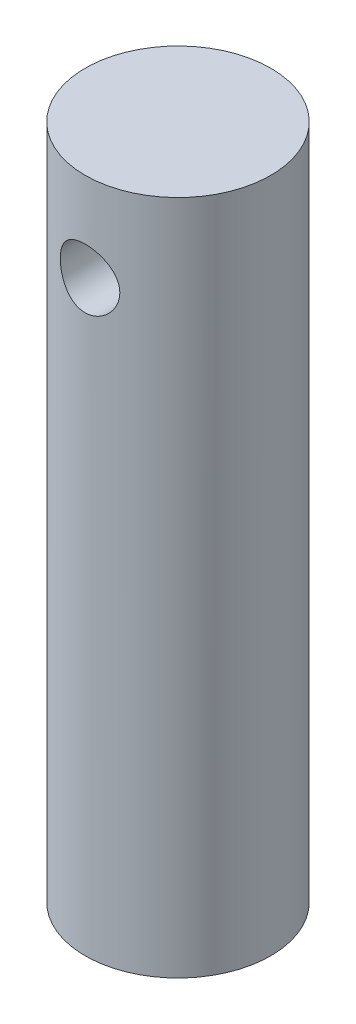
SolidWorks part; units mm, degrees
note: '?' marks a value the reader was unsure of. The reader was unsure of these and kept them because the rebuilt part matched: shared geometry of "Sketch1<3>", "Sketch41<11>", "Sketch41<12>", "Sketch45<3>".
ref_plane "Front Plane" through (0, 0, 0) normal (0, 0, 1) x (1, 0, 0)
ref_plane "Top Plane" through (0, 0, 0) normal (0, 1, 0) x (1, 0, 0)
ref_plane "Right Plane" through (0, 0, 0) normal (1, 0, 0) x (0, 0, -1)
sketch "Sketch1" plane through (0, 0, 0) normal (0, 1, 0) x (1, 0, 0)
  line L0 (0, 32.639) -> (7.239, 39.878)
  line L1 (7.239, 0) -> (55.118, 0)
  line L2 (0, 7.239) -> (0, 32.639)
  line L3 (7.239, 39.878) -> (55.118, 39.878)
  line L4 (7.239, 0) -> (0, 7.239)
  arc A0 (55.118, 0) -> (55.118, 39.878) centre (55.118, 19.939) ccw
  point P0 (0, 0)
  point P2 (0, 39.878)
  dimension "D1" = 55.118
  dimension "D2" = 39.878
extrude "Boss-Extrude1" add sketch "Sketch1" along normal blind 6.35
sketch "Sketch6" plane through (0, 6.35, 0) normal (0, 1, 0) x (1, 0, 0)
  circle A0 centre (55.118, 19.939) radius 19.431
extrude "Boss-Extrude4" add sketch "Sketch6" along normal blind 0.762 separate body contours A0
sketch "Sketch7" plane through (0, 7.112, 0) normal (0, 1, 0) x (1, 0, 0)
  circle A0 centre (55.118, 19.939) radius 19.05
  dimension "D1" = 38.1
extrude "Boss-Extrude5" add sketch "Sketch7" along normal blind 68.326 separate body
sketch "Sketch8" plane through (0, 75.438, 0) normal (0, 1, 0) x (1, 0, 0)
  circle A0 centre (55.118, 19.939) radius 4.953
  dimension "D1" = 9.906
fillet "Fillet6" radius 5.08 2 edges at (0, 3.175, -7.239) (0, 3.175, -32.639)
fillet "Fillet7" radius 1.905 2 edges at (7.239, 3.175, -39.878) (7.239, 3.175, 0)
sketch "Sketch15" plane through (0, 6.35, 0) normal (0, 1, 0) x (1, 0, 0)
  line L0 (35.5603, 29.0153) -> (35.5603, 29.0265)
  line L2 (0, 30.5348) -> (0, 9.3432) construction
  line L3 (0, 19.939) -> (0, 10.2869)
  line L4 (0, 19.939) -> (0, 29.591)
  line L5 (0, 10.2869) -> (16.412, 5.5423)
  line L7 (35.5603, 10.8628) -> (35.5603, 10.8515)
  line L10 (0, 29.591) -> (16.4119, 34.3357)
  arc A0 (16.412, 5.5423) -> (16.4119, 34.3357) centre (20.574, 19.939) ccw
ref_plane "Plane4" through (13.8375, 0, -51.6424) normal (0.2588, 0, -0.9659) x (0, -1, 0)
ref_plane "Plane5" through (12.5227, 0, -46.7355) normal (0.2588, 0, -0.9659) x (0, -1, 0)
sketch "Sketch23" plane through (12.5227, 0, -46.7355) normal (0.2588, 0, -0.9659) x (0, -1, 0)
  line L0 (-6.35, -67.5103) -> (-6.35, -28.6483) construction
  line L1 (-2.032, -53.8839) -> (5.588, -53.8839)
  line L2 (-2.032, -53.8839) -> (-2.032, -42.4539)
  line L3 (-2.032, -42.4539) -> (5.588, -42.4539)
  arc A0 (5.588, -53.8839) -> (5.588, -42.4539) centre (5.588, -48.1689) ccw
  dimension "D1" = 11.43
  dimension "D2" = 7.62
  dimension "D3" = 4.318
extrude "Boss-Extrude15" add sketch "Sketch23" along normal blind 6.35
sketch "Sketch24" plane through (14.1662, 0, -52.8692) normal (0.2588, 0, -0.9659) x (-0.9659, 0, -0.2588)
  circle A0 centre (-48.1689, -5.588) radius 4.064
  dimension "D1" = 8.128
extrude "Boss-Extrude16" add sketch "Sketch24" along normal blind 10.16
sketch "Sketch25" plane through (16.7959, 0, -62.683) normal (0.2588, 0, -0.9659) x (-0.9659, 0, -0.2588)
  circle A0 centre (-48.1689, -5.588) radius 2.54
  dimension "D1" = 5.08
extrude "Boss-Extrude17" add sketch "Sketch25" along normal blind 10.16
extrude "Boss-Extrude19" add sketch "Sketch1<3>" against normal blind 16.51 separate body
sketch "Sketch1<3>" plane through (0, 0, 0) normal (0, 1, 0) x (1, 0, 0) same geometry as "Sketch1"
fillet "Fillet13" radius 1.905 2 edges at (7.239, -8.255, 0) (7.239, -8.255, -39.878)
fillet "Fillet14" radius 5.08 2 edges at (0, -8.255, -32.639) (0, -8.255, -7.239)
sketch "Sketch26" plane through (0, -16.51, 0) normal (0, -1, 0) x (-1, 0, 0)
  line L4 (-20.574, 28.829) -> (-11.684, 28.829)
  line L5 (-20.574, 28.829) -> (-29.464, 28.829)
  line L6 (-11.684, 28.829) -> (-11.684, 11.049)
  line L7 (-11.684, 11.049) -> (-29.464, 11.049)
  line L8 (-29.464, 11.049) -> (-29.464, 28.829)
extrude "Boss-Extrude20" add sketch "Sketch26" along normal blind 18.796 separate body
chamfer "Chamfer1" distance 2.54 angle 45 4 edges at (29.464, -25.908, -28.829) (29.464, -25.908, -11.049) (11.684, -25.908, -11.049) (11.684, -25.908, -28.829)
fillet "Fillet15" radius 2.54 8 edges at (11.684, -25.908, -13.589) (14.224, -25.908, -11.049) (26.924, -25.908, -11.049) (29.464, -25.908, -13.589) (29.464, -25.908, -26.289) (26.924, -25.908, -28.829) (11.684, -25.908, -26.289) (14.224, -25.908, -28.829)
chamfer "Chamfer2" distance 0.762 angle 45 16 edges at (14.3041, -35.306, -11.2423) (20.574, -35.306, -11.049) (26.8439, -35.306, -11.2423) (28.194, -35.306, -12.319) (29.2707, -35.306, -13.6691) (29.464, -35.306, -19.939) (29.2707, -35.306, -26.2089) (28.194, -35.306, -27.559) (26.8439, -35.306, -28.6357) (20.574, -35.306, -28.829) (14.3041, -35.306, -28.6357) (12.954, -35.306, -27.559) (11.8773, -35.306, -26.2089) (11.684, -35.306, -19.939) (11.8773, -35.306, -13.6691) (12.954, -35.306, -12.319)
sketch "Sketch27" plane through (0, 0, -11.049) normal (0, 0, 1) x (1, 0, 0)
  circle A0 centre (20.574, -26.67) radius 3.175
extrude "Cut-Extrude3" cut sketch "Sketch27" against normal blind 19.05
sketch "Sketch28" plane through (0, 75.438, 0) normal (0, 1, 0) x (1, 0, 0)
  circle A0 centre (55.118, 19.939) radius 19.05
extrude "Boss-Extrude22" add sketch "Sketch28" along normal blind 1.27 separate body
sketch "Sketch29" plane through (0, 76.708, 0) normal (0, 1, 0) x (1, 0, 0)
  circle A0 centre (55.118, 19.939) radius 19.05
extrude "Boss-Extrude24" add sketch "Sketch29" along normal blind 3.048 separate body contours A0
extrude "Boss-Extrude25" add sketch "Sketch8" along normal blind 1.27 from surface at 4.318 contours A0 starting at face at (55.118, 79.756, -0.889)
fillet "Fillet16" radius 0.2286 1 edges at (55.118, 81.026, -14.986)
extrude "Boss-Extrude26" add sketch "Sketch15" along normal blind 254.381 separate body contours L5 A0 L10 L4 L3
sketch "Sketch32" plane through (0, 260.731, 0) normal (0, 1, 0) x (1, 0, 0)
  line L0 (0, 10.2869) -> (0, 29.591)
  line L1 (0, 29.591) -> (16.4119, 34.3357)
  line L2 (0, 10.2869) -> (16.412, 5.5423)
  arc A0 (16.412, 5.5423) -> (16.4119, 34.3357) centre (20.574, 19.939) ccw
extrude "Boss-Extrude27" add sketch "Sketch32" along normal blind 8.89 separate body
sketch "Sketch33" plane through (0, 269.621, 0) normal (0, 1, 0) x (1, 0, 0)
  circle A0 centre (20.574, 19.939) radius 9.906
extrude "Boss-Extrude28" add sketch "Sketch33" along normal blind 21.336
sketch3d "3DSketch1" plane through (0, 0, 0) normal (0, 0, 1) x (1, 0, 0)
sketch "Sketch41" plane through (0, 6.35, 0) normal (0, 1, 0) x (1, 0, 0)
  line L0 (16.4119, 34.3357) -> (0, 29.591)
  line L1 (37.5429, 9.0662) -> (33.7712, 12.8379)
  line L2 (0.2737, 32.0497) -> (15.777, 36.5318)
  line L3 (37.5429, 9.0662) -> (31.2567, 2.78)
  line L4 (0, 29.591) -> (0, 30.5348)
  line L5 (0, 30.5348) -> (0.2737, 32.0497)
  line L6 (-0.6349, 31.7871) -> (15.777, 36.5318) construction
  line L7 (0, 19.9389) -> (7.9017, 19.9389)
  line L8 (31.2567, 2.78) -> (27.426, 6.6107)
  line L9 (0, 10.2869) -> (0, 29.591) construction
  line L10 (0, 10.2869) -> (0, 9.3431)
  line L12 (37.5429, 30.8116) -> (33.7712, 27.0399)
  line L13 (37.5429, 30.8116) -> (31.2567, 37.0978)
  line L14 (31.2567, 37.0978) -> (27.426, 33.2671)
  line L15 (0, 9.3431) -> (0.2737, 7.8281)
  line L16 (0.2737, 7.8281) -> (15.777, 3.3461)
  line L17 (16.4119, 5.5422) -> (0, 10.2869)
  line L18 (-0.6349, 8.0908) -> (15.7771, 3.3462) construction
  line L19 (27.426, 33.2671) -> (29.1122, 34.9533)
  line L20 (0, 29.591) -> (16.4119, 34.3357) construction
  line L21 (0, 10.2869) -> (16.412, 5.5423) construction
  arc A0 (16.4119, 34.3357) -> (33.7712, 27.0399) centre (20.574, 19.939) cw
  arc A1 (15.777, 36.5318) -> (29.1122, 34.9533) centre (20.574, 19.939) cw
  arc A2 (16.4119, 34.3357) -> (16.412, 5.5423) centre (20.574, 19.939) cw construction
  arc A3 (15.777, 36.5318) -> (15.7771, 3.3462) centre (20.574, 19.939) cw construction
  arc A4 (16.4119, 34.3357) -> (27.426, 33.2671) centre (20.574, 19.939) cw
  arc A5 (15.777, 3.3461) -> (29.1122, 4.9245) centre (20.574, 19.9389) ccw
  arc A6 (16.4119, 5.5422) -> (33.7712, 12.8379) centre (20.574, 19.9389) ccw
  line M5 (0, 30.5348) -> (0, 9.3432)
  arc M6 (0, 9.3432) -> (1.4879, 5.7511) centre (5.08, 9.3432) ccw
extrude "Boss-Extrude30" add sketch "Sketch41" along normal blind 2.159 separate body contours A1 L2 L5 L0 A0 L14 M5
extrude "Boss-Extrude31" add sketch "Sketch41<11>" along normal blind 2.159 separate body contours A6 L17 L15 L16 A5 L8 M5 M6
sketch "Sketch41<11>" plane through (0, 6.35, 0) normal (0, 1, 0) x (1, 0, 0) same geometry as "Sketch41"
extrude "Boss-Extrude33" add sketch "Sketch41<12>" along normal blind 12.7 separate body contours L14 A0 L12 L13 | A6 L8 L3 L1
sketch "Sketch41<12>" plane through (0, 6.35, 0) normal (0, 1, 0) x (1, 0, 0) same geometry as "Sketch41"
fillet "Fillet17" radius 0.2286 5 edges at (35.657, 19.05, -28.9258) (29.3413, 19.05, -35.1825) (34.3998, 19.05, -33.9547) (37.5429, 12.7, -30.8116) (31.2567, 12.7, -37.0978)
fillet "Fillet18" radius 0.2286 5 edges at (35.657, 19.05, -10.9521) (29.3413, 19.05, -4.6954) (37.5429, 12.7, -9.0662) (34.3998, 19.05, -5.9231) (31.2567, 12.7, -2.78)
sketch "Sketch43" plane through (34.1773, 0, -34.1773) normal (0.7071, 0, -0.7071) x (-0.7071, 0, -0.7071)
  circle A0 centre (-0.3147, 13.7414) radius 3.175
extrude "Boss-Extrude34" add sketch "Sketch43" along normal blind 1.27 separate body
fillet "Fillet19" radius 1.27 1 edges at (33.0527, 13.7414, -37.0978)
sketch "Sketch44" plane through (14.2383, 0, 14.2383) normal (0.7071, 0, 0.7071) x (0.7071, 0, -0.7071)
  circle A0 centre (28.5126, 13.7414) radius 3.175
extrude "Boss-Extrude35" add sketch "Sketch44" along normal blind 1.27 separate body
fillet "Fillet20" radius 1.27 1 edges at (37.5429, 13.7414, -7.2702)
sketch "Sketch45" plane through (0, -16.51, 0) normal (0, -1, 0) x (1, 0, 0)
  line L0 (4.0845, -36.7235) -> (6.681, -39.32)
  line L2 (6.681, -39.32) -> (1.4879, -34.1269) construction
  line L4 (55.118, -39.878) -> (8.0281, -39.878) construction
  line L5 (11.3938, -39.878) -> (8.0281, -39.878)
  line L6 (11.3938, 0) -> (8.0281, 0)
  line L7 (4.0845, -3.1545) -> (6.681, -0.558)
  arc A0 (11.2821, -38.9146) -> (11.3938, -39.878) centre (11.8197, -39.3405) ccw
  arc A1 (11.2821, -38.9146) -> (5.0443, -35.9783) centre (8.8543, -35.9783) ccw
  arc A2 (11.2821, -0.9634) -> (11.3938, 0) centre (11.8197, -0.5375) cw
  arc A3 (5.0443, -35.9783) -> (4.0845, -36.7235) centre (4.1918, -35.871) cw
  arc A4 (5.0443, -3.8997) -> (4.0845, -3.1545) centre (4.1918, -4.007) ccw
  arc A5 (11.2821, -0.9634) -> (5.0443, -3.8997) centre (8.8543, -3.8997) cw
  arc A6 (55.118, -39.878) -> (55.118, 0) centre (55.118, -19.939) ccw construction
  arc A7 (73.6621, -16.9922) -> (73.6621, -22.8858) centre (71.247, -19.939) ccw
  arc A8 (73.6621, -22.8858) -> (74.7121, -23.6317) centre (73.8141, -23.7837) cw
  arc A9 (73.6621, -16.9922) -> (74.7121, -16.2463) centre (73.8141, -16.0943) ccw
  arc A10 (8.0281, -39.878) -> (6.681, -39.32) centre (8.0281, -37.973) cw
  arc A11 (8.0281, 0) -> (6.681, -0.558) centre (8.0281, -1.905) ccw
  arc A12 (74.7121, -23.6317) -> (74.7121, -16.2463) centre (55.118, -19.939) ccw
  line M8 (1.4879, -34.1269) -> (6.681, -39.32)
  arc M9 (6.681, -39.32) -> (8.0281, -39.878) centre (8.0281, -37.973) ccw
  line M10 (8.0281, -39.878) -> (55.118, -39.878)
  line M12 (55.118, 0) -> (8.0281, 0)
  arc M13 (8.0281, 0) -> (6.681, -0.558) centre (8.0281, -1.905) ccw
  line M14 (6.681, -0.558) -> (1.4879, -5.7511)
extrude "Cut-Extrude5" cut sketch "Sketch45" against normal blind 2.54 contours A1 A3 A0 M8 M9 M10 | A5 A2 A4 M12 M13 M14
extrude "Cut-Extrude6" cut sketch "Sketch45<3>" against normal blind 2.54
sketch "Sketch45<3>" plane through (0, -16.51, 0) normal (0, -1, 0) x (1, 0, 0) same geometry as "Sketch45"
sketch "Sketch47" plane through (0, -13.97, 0) normal (0, -1, 0) x (-1, 0, 0)
  circle A0 centre (-8.8543, 35.9783) radius 2.54
  circle A1 centre (-8.8543, 3.8997) radius 2.54
  circle A2 centre (-71.247, 19.939) radius 2.54
extrude "Boss-Extrude36" add sketch "Sketch47" along normal blind 2.54 separate body
fillet "Fillet22" radius 1.524 1 edges at (8.8543, -16.51, -38.5183)
fillet "Fillet23" radius 1.524 1 edges at (8.8543, -16.51, -6.4397)
sketch "Sketch48" plane through (0, 0, 0) normal (-1, 0, 0) x (0, 0, 1)
  circle A0 centre (-19.939, 12.7) radius 3.81
extrude "Boss-Extrude37" add sketch "Sketch48" along normal blind 1.524
fillet "Fillet24" radius 1.524 1 edges at (-1.524, 12.7, -16.129)
fillet "Fillet25" radius 1.524 1 edges at (71.247, -16.51, -22.479)
sketch "Sketch49" plane through (0, 0, 0) normal (-1, 0, 0) x (0, 0, 1)
  line L0 (-19.9389, 260.731) -> (-19.9389, 255.778) construction
  line L1 (-29.591, 260.731) -> (-10.2869, 260.731) construction
  line L2 (-30.5348, 6.35) -> (-9.3432, 6.35) construction
  circle A0 centre (-19.9389, 255.778) radius 3.81
  dimension "Flat Head Screw" = 249.428
extrude "Cut-Extrude7" cut sketch "Sketch49" against normal blind 2.54
sketch "Sketch50" plane through (2.54, 0, 0) normal (-1, 0, 0) x (0, 0, 1)
  circle A0 centre (-19.9389, 255.778) radius 3.556
extrude "Boss-Extrude39" add sketch "Sketch50" along normal blind 2.54 contours A0
sketch "Sketch52" plane through (0, 0, -11.049) normal (0, 0, 1) x (1, 0, 0)
  circle A0 centre (20.574, 281.432) radius 3.175
  circle A1 centre (20.574, -26.67) radius 3.175 construction
  dimension "Hole to Hole" = 308.102
extrude "Cut-Extrude11" cut sketch "Sketch52" against normal through all both and the other way through all
sketch "Sketch55" plane through (0, 269.621, 0) normal (0, 1, 0) x (1, 0, 0)
  line L1 (-50.6869, 71.4849) -> (119.8971, 71.4849)
  line L2 (-50.6869, 71.4849) -> (-50.6869, -43.4683)
  line L3 (-50.6869, -43.4683) -> (119.8971, -43.4683)
  line L4 (119.8971, 71.4849) -> (119.8971, -43.4683)
extrude "Cut-Extrude13" cut sketch "Sketch55" against normal blind 346.202
sketch "Sketch56" plane through (0, 269.621, 0) normal (0, -1, 0) x (1, 0, 0)
  circle A1 centre (20.574, -19.939) radius 9.906
  circle A2 centre (20.574, -19.939) radius 9.906
  dimension "D1" = 0
extrude "Boss-Extrude40" add sketch "Sketch56" along normal blind 50.8
ref_axis "Axis1" through (20.574, 290.957, -19.939) along (0, -1, 0)?
equation "\"Stroke\"= 8"
equation "\"D1@Boss-Extrude26\"= \"Stroke\" + 2.015"
equation "\"Flat Head Screw@Sketch49\"= \"Stroke\" + 1.82"
equation "\"Hole to Hole@Sketch52\"= \"Stroke\" + 4.13"
